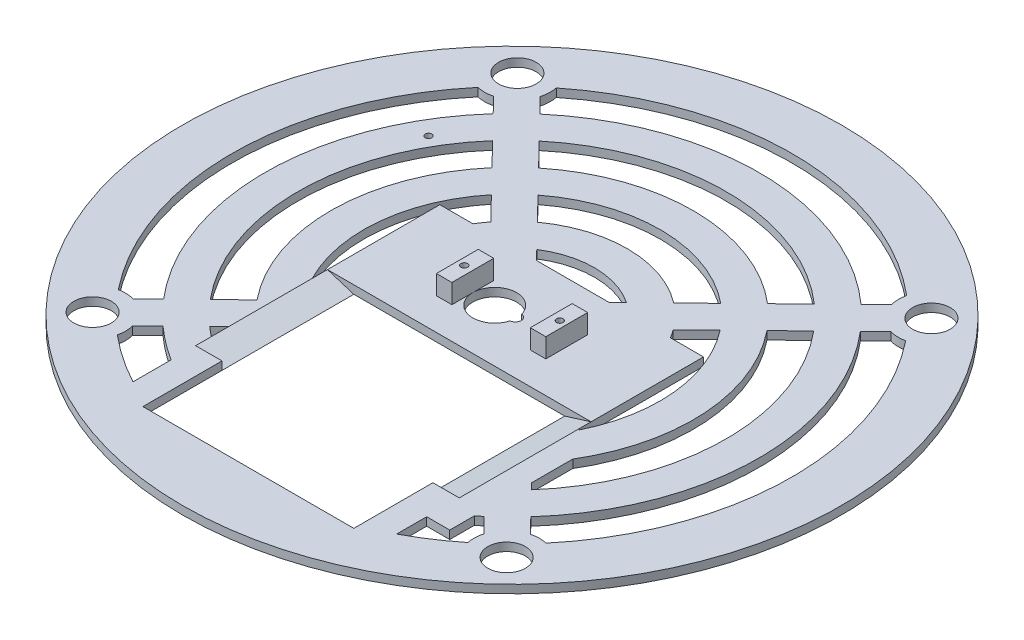
SolidWorks part; units mm, degrees
note: The reader was unsure of these and kept them because the rebuilt part matched: shared geometry of "Çizim4<3>", "Çizim5<3>".
ref_plane "Ön Düzlem" through (0, 0, 0) normal (0, 0, 1) x (1, 0, 0)
ref_plane "Üst Düzlem" through (0, 0, 0) normal (0, 1, 0) x (1, 0, 0)
ref_plane "Sağ Düzlem" through (0, 0, 0) normal (1, 0, 0) x (0, 0, -1)
sketch "Çizim1" plane through (0, 0, 0) normal (0, 1, 0) x (1, 0, 0)
  line L1 (-32, -16) -> (32, -16)
  line L2 (-32, -16) -> (-32, -80)
  line L3 (-32, -80) -> (32, -80)
  line L4 (32, -16) -> (32, -80)
  circle A0 centre (0, 0) radius 100
  point P7 (0, -16)
  dimension "D1" = 200
  dimension "D2" = 16
  dimension "D3" = 64
  dimension "D4" = 64
extrude "Yükseklik-Ekstrüzyon1" add sketch "Çizim1" along normal blind 2.5
sketch "Çizim2" plane through (0, 0, 0) normal (0, -1, 0) x (1, 0, 0)
  arc A2 (0.7808, -1.2542) -> (0.7808, 1.2542) centre (1.01, 0) ccw
  arc A3 (0.7808, 1.2542) -> (0.7808, -1.2542) centre (-5.24, 0) ccw
  arc A4 (1.1708, 1.7677) -> (1.1708, -1.7677) centre (-5.24, 0) ccw
  arc A5 (1.1708, -1.7677) -> (1.1708, 1.7677) centre (1.01, 0) ccw
  arc A9 (0.7808, 1.2542) -> (0.7808, -1.2542) centre (-5.24, 0) ccw construction
  dimension "D4" = 6.15
  dimension "D2" = 6.25
  dimension "D3" = 2.5084
  dimension "D5" = 5.24
  dimension "D1" = 0.5
extrude "Kes-Ekstrüzyon1" cut sketch "Çizim2" against normal through all contours A2 A3 | A4 A5 A3 A2
sketch "Çizim3" plane through (0, 2.5, 0) normal (0, 1, 0) x (1, 0, 0)
  line L0 (-11.89, -6.35) -> (-16.59, -6.35)
  line L5 (-16.59, -6.35) -> (-16.59, 6.35)
  line L10 (-11.89, -6.35) -> (-11.89, 6.35)
  line L11 (-11.89, 6.35) -> (-16.59, 6.35)
  line L12 (-16.39, 6.25) -> (-11.39, 6.25) construction
  line L13 (-11.39, -6.25) -> (-16.39, -6.25) construction
  line L14 (-16.49, -6.15) -> (-16.49, -0.6) construction
  line L15 (-11.59, 6.15) -> (-11.59, -6.15) construction
  line L16 (16.61, -6.35) -> (11.91, -6.35)
  line L17 (11.91, -6.35) -> (11.91, 6.35)
  line L18 (16.61, -6.35) -> (16.61, 6.35)
  line L19 (16.61, 6.35) -> (11.91, 6.35)
  line L20 (11.41, 6.25) -> (16.51, 6.25) construction
  line L21 (16.51, 6.25) -> (16.51, 0.5) construction
  line L22 (16.51, -6.25) -> (11.41, -6.25) construction
  line L23 (11.61, -6.15) -> (11.61, 6.15) construction
  circle A4 centre (14.51, 0) radius 1
  circle A5 centre (-14.49, 0) radius 1
  dimension "D1" = 0.1
  dimension "D2" = 0.1
  dimension "D3" = 0.1
  dimension "D4" = 0.3
  dimension "D5" = 0.1
  dimension "D6" = 0.1
  dimension "D7" = 0.1
  dimension "D8" = 0.3
extrude "Yükseklik-Ekstrüzyon2" add sketch "Çizim3" along normal up to surface (5.85 mm away)
sketch "Çizim4" plane through (0, 0, 0) normal (0, -1, 0) x (1, 0, 0)
  line L0 (32, 80) -> (32, 16) construction
  line L1 (32, 57.8915) -> (39, 57.8915)
  line L2 (32, 57.8915) -> (32, 27.8915)
  line L3 (32, 27.8915) -> (39, 27.8915)
  line L4 (39, 57.8915) -> (39, 27.8915)
  line L9 (35, 57.8915) -> (35, 27.8915)
  line M14 (32, 80) -> (32, 16)
  dimension "D1" = 7
  dimension "D2" = 4
  dimension "D3" = 30
extrude "Yükseklik-Ekstrüzyon3" add sketch "Çizim4" along normal blind 4 contours L1 L9 L3 L4
extrude "Yükseklik-Ekstrüzyon4" add sketch "Çizim4<3>" along normal blind 3 from surface at 4 contours L9 L1 L3 M14 | L1 L9 L3 L4 starting at face at (37, -4, 42.8915)
sketch "Çizim4<3>" plane through (0, 0, 0) normal (0, -1, 0) x (1, 0, 0) same geometry as "Çizim4"
sketch "Çizim5" plane through (0, 0, 0) normal (0, -1, 0) x (1, 0, 0)
  circle A0 centre (-21.1437, -10.4346) radius 3
  circle A2 centre (-21.1437, -10.4346) radius 5
  dimension "D1" = 6
  dimension "D2" = 2
extrude "Yükseklik-Ekstrüzyon5" add sketch "Çizim5" along normal up to surface (3 mm away) contours A0
extrude "Yükseklik-Ekstrüzyon6" add sketch "Çizim5<3>" along normal blind 2 from surface at 3
sketch "Çizim5<3>" plane through (0, 0, 0) normal (0, -1, 0) x (1, 0, 0) same geometry as "Çizim5"
sketch "Çizim11" plane through (0, 0, 0) normal (0, -1, 0) x (1, 0, 0)
  circle A0 centre (-59.798, -34.4695) radius 1
extrude "Kes-Ekstrüzyon5" cut sketch "Çizim11" against normal through all
sketch "Çizim12" plane through (0, 0, 0) normal (0, -1, 0) x (1, 0, 0)
  circle A0 centre (0, 0) radius 90
  circle A1 centre (-64.4557, 62.8129) radius 5.7
  circle A2 centre (62.8129, 64.4557) radius 5.7
  circle A3 centre (64.4557, -62.8129) radius 5.7
  circle A4 centre (-62.8129, -64.4557) radius 5.7
  point P14 (0, 0)
  dimension "D1" = 180
  dimension "D2" = 11.4
  dimension "D3" = 4
extrude "Kes-Ekstrüzyon6" cut sketch "Çizim12" against normal through all contours A1 | A2 | A4 | A3
sketch "Çizim13" plane through (0, 2.5, 0) normal (0, 1, 0) x (1, 0, 0)
  line L0 (-32, -16) -> (-32, -80) construction
  line L1 (32, -80) -> (32, -16) construction
  line L2 (-32, -80) -> (32, -80) construction
  line L3 (-32, 10.1034) -> (-32, -80)
  line L4 (32, -80) -> (32, -57.8915)
  line L5 (-32, -80) -> (32, -80)
  line L6 (39, -27.8915) -> (32, -27.8915) construction
  line L7 (39, -57.8915) -> (32, -57.8915) construction
  line L8 (39, -57.8915) -> (39, -27.8915) construction
  line L9 (39, -27.8915) -> (32, -27.8915)
  line L10 (39, -57.8915) -> (32, -57.8915)
  line L11 (39, -57.8915) -> (39, -27.8915)
  line L12 (32, -27.8915) -> (32, 10.1034)
  line L13 (-32, 10.1034) -> (32, 10.1034)
  line L14 (-40, 18.1034) -> (40, 18.1034)
  line L15 (40, -19.8915) -> (40, 18.1034)
  line L16 (47, -19.8915) -> (40, -19.8915)
  line L17 (47, -65.8915) -> (47, -19.8915)
  line L18 (47, -65.8915) -> (40, -65.8915)
  line L19 (40, -88) -> (40, -65.8915)
  line L20 (-40, -88) -> (40, -88)
  line L21 (-40, 18.1034) -> (-40, -88)
  line L28 (-87.8731, -85.6335) -> (90.057, 87.7617) construction
  line L30 (89.8923, -92.2433) -> (-94.4137, 96.8829) construction
  line L31 (-88.9798, 84.1428) -> (82.1418, -91.4542)
  line L32 (-88.9798, 84.1428) -> (-81.8181, 91.122)
  line L33 (82.1418, -91.4542) -> (89.3035, -84.475)
  line L34 (-81.8181, 91.122) -> (89.3035, -84.475)
  line L35 (82.709, 87.5826) -> (-86.9645, -77.7665)
  line L36 (82.709, 87.5826) -> (89.6883, 80.4209)
  line L37 (-86.9645, -77.7665) -> (-79.9853, -84.9282)
  line L38 (89.6883, 80.4209) -> (-79.9853, -84.9282)
  circle A0 centre (0, 0) radius 100 construction
  circle A1 centre (0, 0) radius 100
  circle A3 centre (0, 0) radius 90
  circle A4 centre (-64.4557, -62.8129) radius 10
  circle A5 centre (-62.8129, 64.4557) radius 10
  circle A6 centre (64.4557, 62.8129) radius 10
  circle A7 centre (62.8129, -64.4557) radius 10
  circle A8 centre (0, 0) radius 15
  circle A9 centre (0, 0) radius 25
  circle A10 centre (0, 0) radius 35
  circle A11 centre (0, 0) radius 45
  circle A12 centre (0, 0) radius 55
  circle A13 centre (0, 0) radius 65
  circle A14 centre (0, 0) radius 75
  circle A15 centre (0, 0) radius 85
  circle A16 centre (0, 0) radius 95
  point P35 (0, 0)
  point P54 (-85.3989, 87.6324)
  point P64 (86.1987, 84.0017)
  dimension "D4" = 30
  dimension "D13" = 10
  dimension "D14" = 10
  dimension "D1" = 8
  dimension "D2" = 10
  dimension "D5" = 10
  dimension "D6" = 10
  dimension "D7" = 10
  dimension "D8" = 10
  dimension "D9" = 10
  dimension "D10" = 10
  dimension "D11" = 10
  dimension "D12" = 10
  dimension "D3" = 4
extrude "Kes-Ekstrüzyon7" cut sketch "Çizim13" against normal through all contours L34 A13 L38 A12 L17 | L16 A11 L38 A10 L14 L15 | A7 A15 A6 L38 A14 L34 | A6 A15 A5 L34 A14 L35 | L35 A13 L34 A12 | L35 A11 L34 A10 | L35 A9 L34 L14 | L31 A11 L21 L14 A10 | L31 A13 L35 A12 | A5 A15 A4 L35 A14 L31 | A4 A15 L21 A14 L38 | L38 A13 L21 | L19 A15 A7 L31 A14 L17 L18
ref_plane "Düzlem1" through (0, 0, 16) normal (0, 0, 1) x (1, 0, 0)
sketch "Çizim14" plane through (0, 0, 16) normal (0, 0, 1) x (1, 0, 0)
  line L0 (-32, 0) -> (-32, 2.5)
  line L1 (-32, 2.5) -> (-40, 2.5)
  line L2 (-40, 2.5) -> (-32, 0)
  line L3 (32, 2.5) -> (32, 0)
  line L4 (32, 0) -> (40, 2.5)
  line L5 (40, 2.5) -> (32, 2.5)
  dimension "D1" = 8
  dimension "D2" = 8
extrude "Kes-Ekstrüzyon8" cut sketch "Çizim14" along normal blind 40
